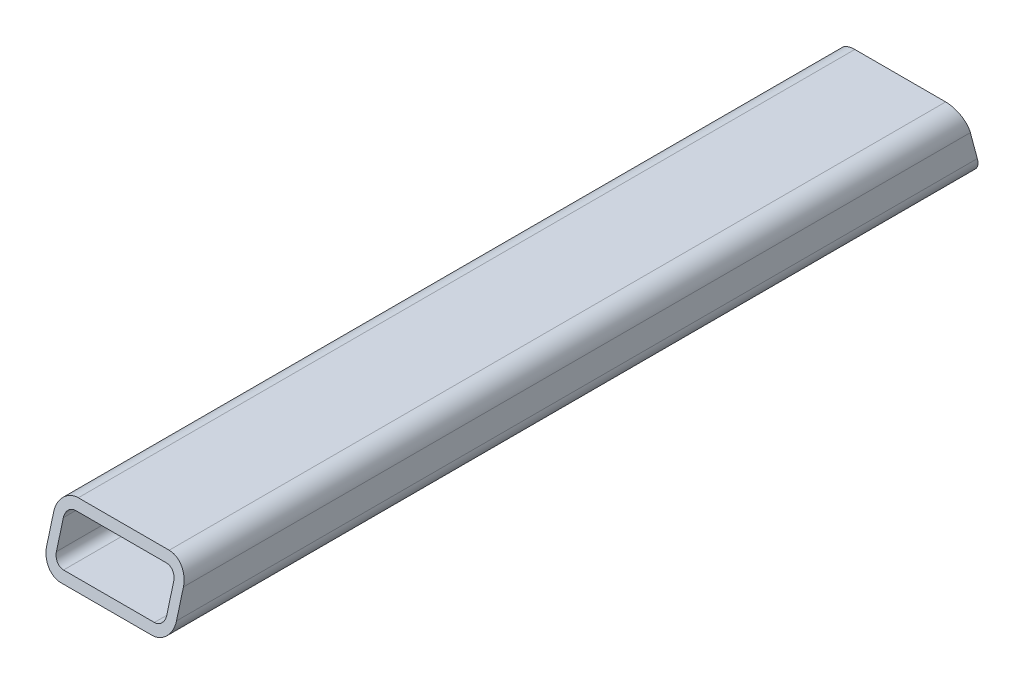
SolidWorks part; units mm, degrees
material "Ст 3 ГОСТ 380-88"
ref_plane "Спереди" through (0, 0, 0) normal (0, 0, 1) x (1, 0, 0)
ref_plane "Сверху" through (0, 0, 0) normal (0, 1, 0) x (1, 0, 0)
ref_plane "Справа" through (0, 0, 0) normal (1, 0, 0) x (0, 0, -1)
sketch "Эскиз1" plane through (0, 0, 0) normal (0, 0, 1) x (1, 0, 0)
  line L1 (-14, 10) -> (14, 10)
  line L2 (-20, 4) -> (-20, -4)
  line L3 (-14, -10) -> (14, -10)
  line L4 (20, 4) -> (20, -4)
  line L5 (-20, 10) -> (20, -10) construction
  line L6 (-20, -10) -> (20, 10) construction
  arc A0 (14, -10) -> (20, -4) centre (14, -4) ccw
  arc A1 (-14, 10) -> (-20, 4) centre (-14, 4) ccw
  arc A2 (-20, -4) -> (-14, -10) centre (-14, -4) ccw
  arc A3 (14, 10) -> (20, 4) centre (14, 4) cw
  point P0 (0, 0)
  dimension "D3" = 6
  dimension "D4" = 6
  dimension "D1" = 20
  dimension "D2" = 40
extrude "Бобышка-Вытянуть1" add sketch "Эскиз1" along normal blind 125 and the other way blind 125
shell "Оболочка1" thickness 3 removed face at (0, 0, -125) removed face at (0, 0, 125)
chamfer "Фаска1" distance 20 angle 15 2 edges at (0, 10, -125) (0, 10, 125) tangent propagation no first distance on face at (0, 0, -125) first distance on face at (0, 0, 125)
